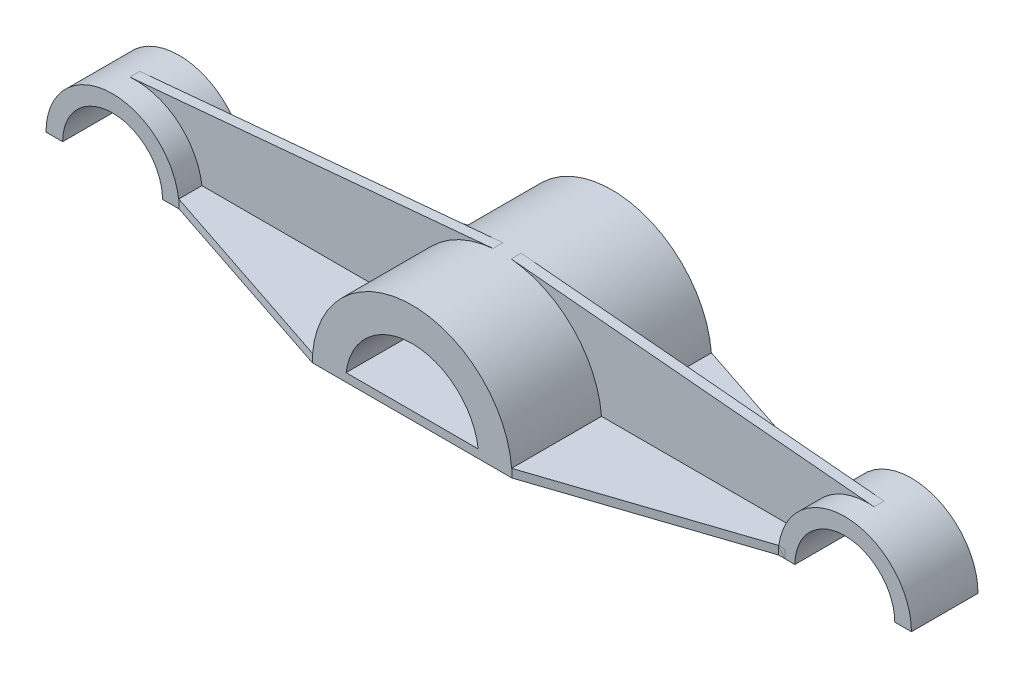
SolidWorks part; units mm, degrees
ref_plane "Front Plane" through (0, 0, 0) normal (0, 0, 1) x (1, 0, 0)
ref_plane "Top Plane" through (0, 0, 0) normal (0, 1, 0) x (1, 0, 0)
ref_plane "Right Plane" through (0, 0, 0) normal (1, 0, 0) x (0, 0, -1)
sketch "Sketch1" plane through (0, 0, 0) normal (0, 0, 1) x (1, 0, 0)
  line L0 (0, -55) -> (0, 55) construction
  line L1 (-130, 0) -> (-125, 0)
  line L2 (90, 0) -> (95, 0)
  line L3 (125, 0) -> (130, 0)
  line L4 (20, 0) -> (30, 0)
  line L5 (-30, 0) -> (-20, 0)
  line L6 (-95, 0) -> (-90, 0)
  arc A0 (30, 0) -> (-30, 0) centre (0, 0) ccw
  arc A1 (20, 0) -> (-20, 0) centre (0, 0) ccw
  arc A2 (-95, 0) -> (-125, 0) centre (-110, 0) ccw
  arc A3 (-90, 0) -> (-130, 0) centre (-110, 0) ccw
  arc A4 (90, 0) -> (130, 0) centre (110, 0) cw
  arc A5 (95, 0) -> (125, 0) centre (110, 0) cw
  dimension "D1" = 60
  dimension "D2" = 40
  dimension "D3" = 30
  dimension "D4" = 40
  dimension "D5" = 110
extrude "Boss-Extrude1" add sketch "Sketch1" along normal mid plane 60 contours A0 L5 A1 L4
extrude "Boss-Extrude2" add sketch "Sketch1<3>" along normal mid plane 20 separate body contours A3 L1 A2 L6
sketch "Sketch1<3>" plane through (0, 0, 0) normal (0, 0, 1) x (1, 0, 0) same geometry as "Sketch1"
extrude "Boss-Extrude3" add sketch "Sketch1<4>" along normal mid plane 20 separate body contours A4 L3 A5 L2
sketch "Sketch1<4>" plane through (0, 0, 0) normal (0, 0, 1) x (1, 0, 0) same geometry as "Sketch1"
sketch "Sketch4" plane through (0, 0, 0) normal (0, 1, 0) x (1, 0, 0)
  line L0 (-90, 10) -> (-30, 30)
  line L1 (-30, 30) -> (30, 30)
  line L2 (30, 30) -> (90, 10)
  line L4 (90, -10) -> (30, -30)
  line L5 (30, -30) -> (-30, -30)
  line L6 (-30, -30) -> (-90, -10)
  line L8 (-90, 10) -> (-92, 10)
  line L9 (-90, 10) -> (-130, 10) construction
  line L10 (-92, 10) -> (-92, -10)
  line L11 (-130, -10) -> (-90, -10) construction
  line L12 (-92, -10) -> (-90, -10)
  line L13 (-90, -10) -> (-90, 10) construction
  line L14 (90, 10) -> (92, 10)
  line L15 (130, 10) -> (90, 10) construction
  line L16 (92, 10) -> (92, -10)
  line L17 (90, -10) -> (130, -10) construction
  line L18 (92, -10) -> (90, -10)
  line L19 (90, -10) -> (90, 10) construction
  dimension "D1" = 2
  dimension "D2" = 2
extrude "Boss-Extrude4" add sketch "Sketch4" along normal blind 2.5
sketch "Sketch7" plane through (0, 0, 0) normal (0, 0, 1) x (1, 0, 0)
  line L4 (-111.8182, 19.9172) -> (-2.7273, 29.8758)
  line L8 (-90, 0) -> (-30, 0) construction
  line L10 (-90, 0) -> (-30, 0)
  arc A2 (-90, 0) -> (-130, 0) centre (-110, 0) ccw construction
  arc A3 (30, 0) -> (-30, 0) centre (0, 0) ccw construction
  arc A8 (-90, 0) -> (-111.8182, 19.9172) centre (-110, 0) ccw
  arc A9 (-2.7273, 29.8758) -> (-30, 0) centre (0, 0) ccw
  point P0 (-6.205, 29.3513)
  point P6 (-5.5895, 29.4747)
  point P20 (-118.1814, 19.3363)
extrude "Boss-Extrude5" add sketch "Sketch7" along normal blind 3
mirror "Mirror1" about plane through (0, 0, 0) normal (1, 0, 0) of "Boss-Extrude5"
